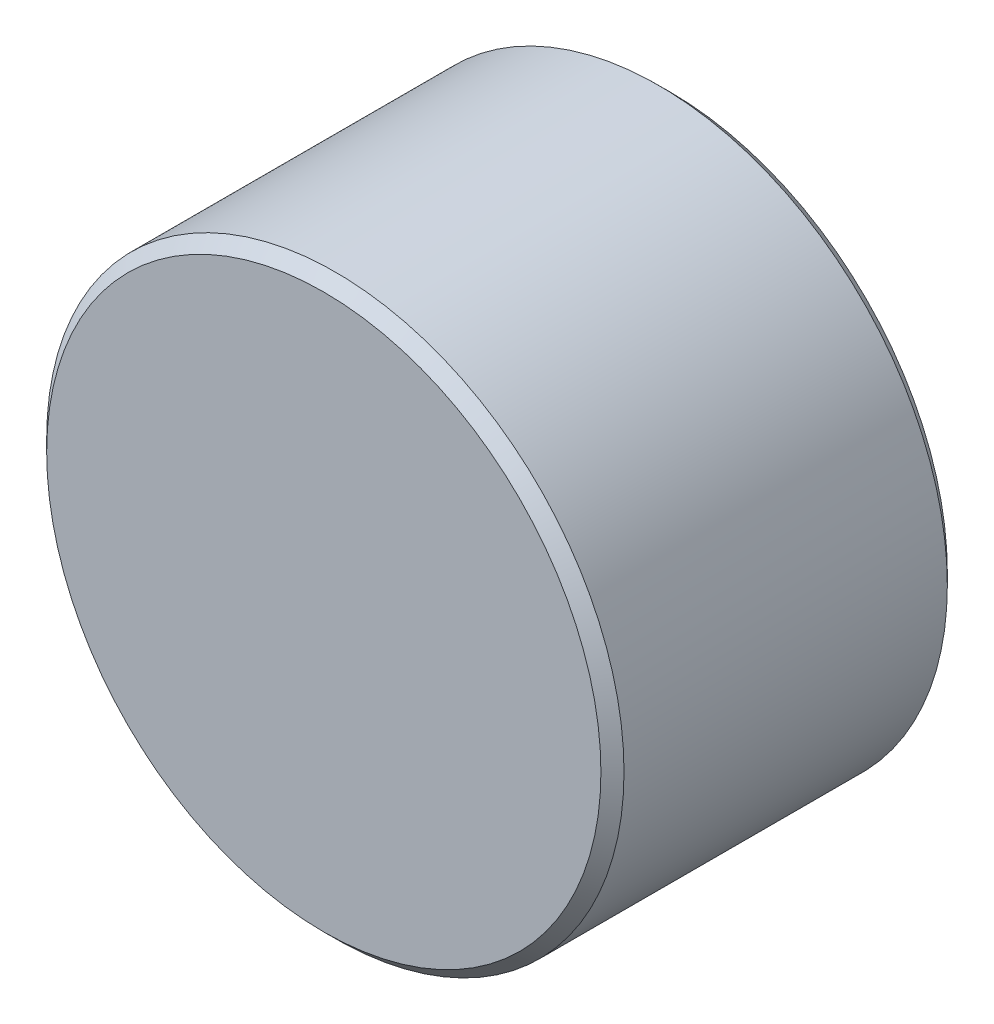
SolidWorks part; units mm, degrees
ref_plane "Front Plane" through (0, 0, 0) normal (0, 0, 1) x (1, 0, 0)
ref_plane "Top Plane" through (0, 0, 0) normal (0, 1, 0) x (1, 0, 0)
ref_plane "Right Plane" through (0, 0, 0) normal (1, 0, 0) x (0, 0, -1)
sketch "Sketch1" plane through (0, 0, 0) normal (0, 0, 1) x (1, 0, 0)
  circle A0 centre (0, 0) radius 2.5
  dimension "D1" = 5
extrude "Boss-Extrude1" add sketch "Sketch1" along normal blind 3
chamfer "Chamfer1" distance 0.1 angle 45 2 edges at (2.5, 0, 0) (2.5, 0, 3)
